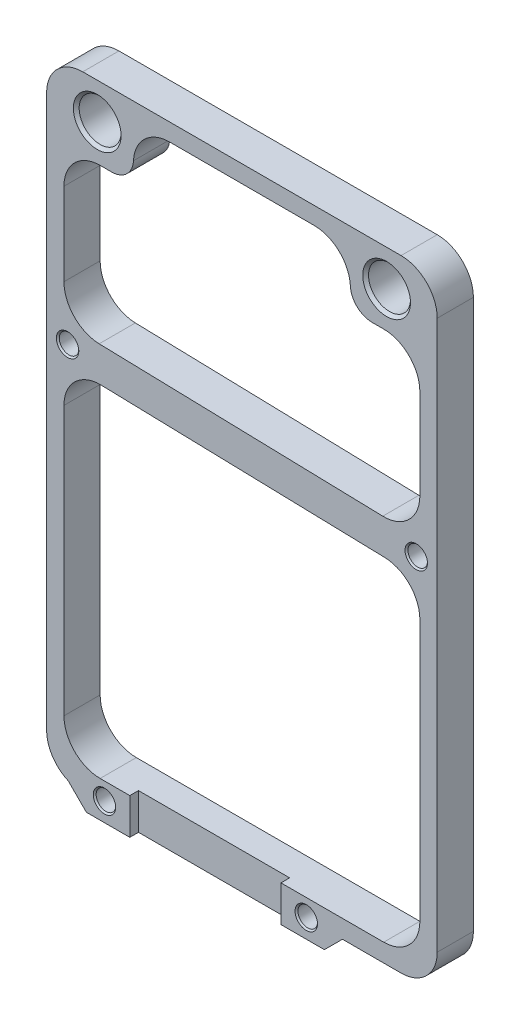
SolidWorks part; units mm, degrees
ref_plane "Front" through (0, 0, 0) normal (0, 0, 1) x (1, 0, 0)
ref_plane "Top" through (0, 0, 0) normal (0, 1, 0) x (1, 0, 0)
ref_plane "Right" through (0, 0, 0) normal (1, 0, 0) x (0, 0, -1)
sketch "Sketch1" plane through (0, 0, 0) normal (0, 0, 1) x (1, 0, 0)
  line L0 (0, 78.4) -> (54, 78.4) construction
  line L1 (0, 0) -> (54, 0)
  line L2 (0, 0) -> (0, 83.4)
  line L3 (5, 88.4) -> (49, 88.4)
  line L4 (54, 0) -> (54, 83.4)
  line L5 (27, 8.5492) -> (27, -24.6289) construction
  circle A0 centre (7, 83.4) radius 2.9
  circle A1 centre (47, 83.4) radius 2.9
  arc A2 (49, 88.4) -> (54, 83.4) centre (49, 83.4) cw
  arc A3 (5, 88.4) -> (0, 83.4) centre (5, 83.4) ccw
  circle A4 centre (2.9, 54.7) radius 1.35
  circle A5 centre (51.1, 53.4) radius 1.35
  circle A6 centre (8, 2.6) radius 1.35
  circle A7 centre (35.9, 2.6) radius 1.35
  dimension "D1" = 5.8
  dimension "D6" = 5
  dimension "D8" = 2.7
  dimension "D10" = 5.1
  dimension "D12" = 50.8
  dimension "D13" = 15.2
  dimension "D14" = 24.1
  dimension "D16" = 25
  dimension "D17" = 2.6
  dimension "D2" = 40
  dimension "D3" = 7
  dimension "D4" = 5
  dimension "D5" = 7
  dimension "D7" = 10
  dimension "D9" = 27.9
  dimension "D11" = 1.3
  dimension "D15" = 27
extrude "Boss-Extrude1" add sketch "Sketch1" along normal blind 5
sketch "Sketch2" plane through (0, 0, 5) normal (0, 0, 1) x (1, 0, 0)
  line L0 (5.5, 0) -> (3, 2.5)
  line L1 (0, 0) -> (54, 0) construction
  line L2 (3, 2.5) -> (0, 2.5)
  line L3 (0, 83.4) -> (0, 0) construction
  line L4 (0, 2.5) -> (0, 0)
  line L5 (0, 0) -> (5.5, 0)
  line L6 (38.4, 0) -> (40.9, 2.5)
  line L7 (40.9, 2.5) -> (54, 2.5)
  line L8 (54, 0) -> (54, 83.4) construction
  line L9 (54, 2.5) -> (54, 0)
  line L10 (54, 0) -> (38.4, 0)
  circle A0 centre (8, 2.6) radius 1.35 construction
  circle A1 centre (35.9, 2.6) radius 1.35 construction
  point P18 (0, 0)
  dimension "D3" = 5
  dimension "D1" = 2.5
  dimension "D2" = 45
  dimension "D4" = 5
extrude "Cut-Extrude1" cut sketch "Sketch2" against normal blind 5
sketch "Sketch3" plane through (0, 0, 5) normal (0, 0, 1) x (1, 0, 0)
  line L0 (12, 81) -> (12, 78.4)
  line L1 (12, 78.4) -> (7.4, 78.4)
  line L2 (2.4, 73.4) -> (2.4, 61.9696)
  line L3 (7.2679, 56.9714) -> (46.4679, 55.9356)
  line L4 (51.6, 60.9339) -> (51.6, 73.4)
  line L5 (46.6, 78.4) -> (42, 78.4)
  line L6 (42, 78.4) -> (42, 81)
  line L7 (37, 86) -> (17, 86)
  line L8 (49, 88.4) -> (5, 88.4) construction
  line L9 (54, 2.5) -> (54, 83.4) construction
  line L10 (0, 83.4) -> (0, 2.5) construction
  line L11 (7.5321, 52.1644) -> (46.7321, 51.1286)
  line L12 (51.6, 46.1304) -> (51.6, 10)
  line L13 (46.6, 5) -> (7.4, 5)
  line L14 (2.4, 10) -> (2.4, 47.1661)
  circle A0 centre (7, 83.4) radius 2.9 construction
  circle A1 centre (47, 83.4) radius 2.9 construction
  circle A3 centre (2.9, 54.7) radius 1.35 construction
  circle A4 centre (51.1, 53.4) radius 1.35 construction
  circle A5 centre (8, 2.6) radius 1.35 construction
  arc A6 (51.6, 10) -> (46.6, 5) centre (46.6, 10) cw
  arc A7 (7.4, 5) -> (2.4, 10) centre (7.4, 10) cw
  arc A8 (2.4, 47.1661) -> (7.5321, 52.1644) centre (7.4, 47.1661) cw
  arc A9 (51.6, 46.1304) -> (46.7321, 51.1286) centre (46.6, 46.1304) ccw
  arc A10 (51.6, 60.9339) -> (46.4679, 55.9356) centre (46.6, 60.9339) cw
  arc A11 (2.4, 61.9696) -> (7.2679, 56.9714) centre (7.4, 61.9696) ccw
  arc A12 (2.4, 73.4) -> (7.4, 78.4) centre (7.4, 73.4) cw
  arc A13 (51.6, 73.4) -> (46.6, 78.4) centre (46.6, 73.4) ccw
  arc A14 (42, 81) -> (37, 86) centre (37, 81) ccw
  arc A15 (12, 81) -> (17, 86) centre (17, 81) cw
  point P34 (2.4, 52.3)
  point P37 (51.6, 51)
  point P40 (51.6, 55.8)
  point P43 (2.4, 57.1)
  dimension "D3" = 5
  dimension "D7" = 2.4
  dimension "D13" = 2.4
  dimension "D14" = 5
  dimension "D1" = 5
  dimension "D2" = 5
  dimension "D4" = 2.4
  dimension "D5" = 2.4
  dimension "D6" = 2.4
  dimension "D8" = 2.4
  dimension "D9" = 2.4
  dimension "D10" = 2.4
  dimension "D11" = 2.4
  dimension "D12" = 2.4
extrude "Cut-Extrude2" cut sketch "Sketch3" against normal blind 5
chamfer "Chamfer1" distance 0.4 angle 45 4 edges at (49.9, 83.4, 0) (49.9, 83.4, 5) (9.9, 83.4, 0) (9.9, 83.4, 5)
chamfer "Chamfer2" distance 0.2 angle 45 8 edges at (37.25, 2.6, 0) (37.25, 2.6, 5) (9.35, 2.6, 0) (9.35, 2.6, 5) (52.45, 53.4, 0) (52.45, 53.4, 5) (4.25, 54.7, 0) (4.25, 54.7, 5)
fillet "Fillet1" radius 3 2 edges at (42, 78.4, 2.5) (12, 78.4, 2.5)
fillet "Fillet2" radius 5 2 edges at (54, 2.5, 2.5) (0, 2.5, 2.5)
sketch "Sketch4" plane through (0, 0, 5) normal (0, 0, 1) x (1, 0, 0)
  line L5 (7.4, 5) -> (46.6, 5) construction
  line L6 (11.5, 5) -> (32.4, 5)
  line L7 (11.5, 5) -> (11.5, 0)
  line L8 (11.5, 0) -> (32.4, 0)
  line L9 (32.4, 5) -> (32.4, 0)
  line L10 (5.5, 0) -> (38.4, 0) construction
  circle A0 centre (8, 2.6) radius 1.35 construction
  circle A1 centre (35.9, 2.6) radius 1.35 construction
  dimension "D1" = 3.5
  dimension "D2" = 3.5
extrude "Cut-Extrude3" cut sketch "Sketch4" against normal blind 1.2
